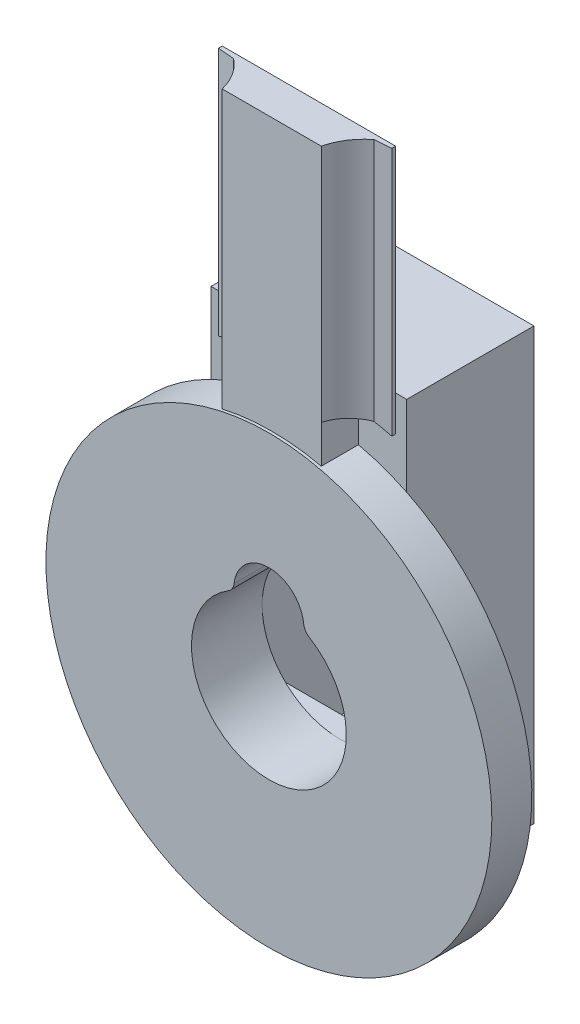
SolidWorks part; units mm, degrees
ref_plane "Front Plane" through (0, 0, 0) normal (0, 0, 1) x (1, 0, 0)
ref_plane "Top Plane" through (0, 0, 0) normal (0, 1, 0) x (1, 0, 0)
ref_plane "Right Plane" through (0, 0, 0) normal (1, 0, 0) x (0, 0, -1)
sketch "Croquis1" plane through (0, 0, 0) normal (0, 0, 1) x (1, 0, 0)
  circle A0 centre (0, 0) radius 18
extrude "Saliente-Extruir1" add sketch "Croquis1" along normal blind 3.5
sketch "Croquis2" plane through (0, 0, 0) normal (0, 0, 1) x (1, 0, 0)
  line L0 (-4, 17.5499) -> (-4, 39.1116)
  line L1 (4, 39.1116) -> (4, 17.5499)
  line L2 (-7, 19.799) -> (-7, 39.928)
  line L3 (-7, 39.928) -> (7, 39.928)
  line L4 (7, 39.928) -> (7, 19.799)
  line L5 (-4, 39.1116) -> (-4, 39.928)
  line L6 (4, 39.1116) -> (4, 39.928)
  arc A0 (4, 17.5499) -> (-4, 17.5499) centre (0, 0) ccw
  arc A1 (10.1584, 18.3795) -> (-10.1584, 18.3795) centre (0, 0) ccw
  arc A2 (-10.1584, 18.3795) -> (-7, 39.928) centre (-213.2982, 59.16) ccw
  arc A3 (10.1584, 18.3795) -> (7, 39.928) centre (213.2982, 59.16) cw
  dimension "D1" = 8
extrude "Saliente-Extruir5" add sketch "Croquis2" along normal blind 3.27 contours A1 L4 L3 L6 L1 | L1 A1 L0 A0 | A1 L1 L6 L3 L5 L0 | A1 L0 L5 L3 L2
ref_plane "Plano1" through (0, 40, 0) normal (0, 1, 0) x (1, 0, 0)
sketch "Croquis5" plane through (0, 40, 0) normal (0, 1, 0) x (1, 0, 0)
  line L1 (-7, -3.27) -> (-7, 0) construction
  line L9 (-7, 0) -> (-7, -0.27)
  line L10 (-7, -0.27) -> (7, -0.27)
  line L11 (7, -0.27) -> (7, 0)
  line L13 (7, 0) -> (-7, 0)
  line L15 (-7, -0.27) -> (-7, 0)
  line L16 (-7, -0.27) -> (-18.8879, -0.27)
  line L17 (-18.8879, -0.27) -> (-18.8879, 0.2021)
  line L18 (-18.8879, 0.2021) -> (18.2421, 0.2021)
  line L19 (18.2421, 0.2021) -> (18.2421, -0.27)
  line L20 (18.2421, -0.27) -> (7, -0.27)
extrude "Cortar-Extruir4" cut sketch "Croquis5" against normal up to surface (58.001 mm away) contours L11 L13 L9 L10 | L20 L19 L18 L17 L16 L9 L13 L11
sketch "Croquis4" plane through (0, 40, 0) normal (0, 1, 0) x (1, 0, 0)
  line L3 (-7, 0) -> (-7, -0.5733)
  line L5 (-4.4792, 0) -> (-7, 0)
  line L7 (0, 0) -> (0, -1.8016)
  line L8 (-4, -3.27) -> (-4.4792, 0)
  line L9 (-7, -0.5733) -> (-5.666, -0.685)
  line L10 (-7, 0) -> (-7, -3.27)
  line L11 (-7, -3.27) -> (-7, -0.27) construction
  line L12 (-4, -3.27) -> (-7, -3.27)
  line L13 (4, -3.27) -> (7, -3.27)
  line L14 (7, 0) -> (7, -3.27)
  line L15 (4.4792, 0) -> (7, 0)
  line L16 (4, -3.27) -> (4.4792, 0)
  line L17 (7, -0.5733) -> (5.666, -0.685)
  line L18 (7, 0) -> (7, -0.5733)
  line L19 (-7, -0.5733) -> (-7, -3.27)
  line L20 (0, -1.8016) -> (0, -3.27)
  line L21 (-4, -3.27) -> (4, -3.27) construction
  line L22 (0, -3.27) -> (-4, -3.27)
  line L23 (-7, -3.27) -> (7, -3.27) construction
  line L24 (0, -3.27) -> (4, -3.27)
  arc A2 (-5.666, -0.685) -> (-4, -3.27) centre (-8.5291, -4.3596) cw
  arc A3 (5.666, -0.685) -> (4, -3.27) centre (8.5291, -4.3596) ccw
  dimension "D1" = 4
  dimension "D2" = 4
extrude "Cortar-Extruir2" cut sketch "Croquis4" against normal blind 21 contours A2 L9 L10 L12 | L17 A3 L13 L14
sketch "Croquis6" plane through (0, 0, 0) normal (0, 0, 1) x (1, 0, 0)
  arc A0 (-3.2771, 5.3219) -> (3.2771, 5.3219) centre (0, 0) ccw
  arc A1 (2.8076, 6.0627) -> (-2.8076, 6.0627) centre (0, 5.75) ccw
  arc A2 (2.8076, 6.0627) -> (3.2771, 5.3219) centre (3.8015, 6.1734) ccw
  arc A3 (-2.8076, 6.0627) -> (-3.2771, 5.3219) centre (-3.8015, 6.1734) cw
extrude "Cortar-Extruir5" cut sketch "Croquis6" along normal blind 10
ref_plane "Plano2" through (0, 0, 0.27) normal (0, 0, -1) x (-1, 0, 0)
sketch "Croquis7" plane through (0, 0, 0) normal (0, 0, 1) x (1, 0, 0)
  arc A0 (-3.2771, 5.3219) -> (3.2771, 5.3219) centre (0, 0) ccw
  arc A1 (-2.8076, 6.0627) -> (2.8076, 6.0627) centre (0, 5.75) cw
  arc A2 (-3.2771, 5.3219) -> (-2.8076, 6.0627) centre (-3.8015, 6.1734) ccw
  arc A3 (2.8076, 6.0627) -> (3.2771, 5.3219) centre (3.8015, 6.1734) ccw
  arc A4 (-5.5967, 7.3647) -> (5.5967, 7.3647) centre (0, 0) ccw
  arc A5 (5.5967, 7.3647) -> (5.5967, 7.3647) centre (5.5967, 7.3647) ccw
  arc A6 (-5.5967, 7.3647) -> (5.5967, 7.3647) centre (0, 5.75) cw
  arc A7 (-5.5967, 7.3647) -> (-5.5967, 7.3647) centre (-5.5967, 7.3647) ccw
  dimension "D1" = 3
extrude "Saliente-Extruir6" add sketch "Croquis7" against normal blind 2.2
sketch "Croquis8" plane through (0, 0, 0.27) normal (0, 0, -1) x (-1, 0, 0)
  arc A0 (-5.5967, 7.3647) -> (5.5967, 7.3647) centre (0, 0) ccw
  arc A1 (-5.5967, 7.3647) -> (5.5967, 7.3647) centre (0, 5.75) cw
  circle A2 centre (0, 0) radius 18
extrude "Cortar-Extruir8" cut sketch "Croquis8" along normal blind 0.27 contours A2 A0 A1
sketch "Croquis9" plane through (0, 0, 0.27) normal (0, 0, -1) x (-1, 0, 0)
  line L0 (0, 0) -> (-6.3, 0)
  line L1 (-6.3, 5.2726) -> (-6.3, 19.8726)
  line L2 (-6.3, 19.8726) -> (6.3, 19.8726)
  line L3 (6.3, 19.8726) -> (6.3, -9.3274)
  line L4 (6.3, -9.3274) -> (0, -9.3274)
  line L5 (0, -9.3274) -> (-6.3, -9.3274)
  line L6 (-6.3, -9.3274) -> (-6.3, 5.2726)
  line L8 (-7.9, 5.2726) -> (-7.9, 21.4726)
  line L10 (7.9, 21.4726) -> (7.9, -10.9274)
  line L13 (-7.9, -10.9274) -> (-7.9, 5.2726)
  line L14 (-7.9, 21.4726) -> (-7.9, 22.6726)
  line L15 (-7.9, 22.6726) -> (7.9, 22.6726)
  line L16 (-7.9, -10.9274) -> (-7.9, -12.1274)
  line L17 (6.3, 16.5326) -> (-6.3, 16.5326)
  line L18 (6.3, -6.2774) -> (-6.3, -6.2774)
  line L19 (7.9, 21.4726) -> (7.9, 22.6726)
  line L20 (-7.9, -12.1274) -> (7.9, -12.1274)
  line L21 (-7.9, 21.4726) -> (7.9, 21.4726) construction
  line L22 (7.9, -12.1274) -> (7.9, -10.9274)
  line L24 (0, -10.9274) -> (-7.9, -10.9274) construction
  line L25 (7.9, -10.9274) -> (0, -10.9274) construction
  arc A0 (-3.2771, 5.3219) -> (3.2771, 5.3219) centre (0, 0) ccw
  arc A1 (3.2771, 5.3219) -> (2.8076, 6.0627) centre (3.8015, 6.1734) cw
  arc A3 (-3.2771, 5.3219) -> (-2.8076, 6.0627) centre (-3.8015, 6.1734) ccw
  arc A4 (2.8076, 6.0627) -> (-2.8076, 6.0627) centre (0, 5.75) ccw
  dimension "D1" = 14.6
  dimension "D2" = 14.6
  dimension "D3" = 6.3
  dimension "D4" = 6.3
  dimension "D5" = 1.6
  dimension "D6" = 1.2
  dimension "D7" = 1.2
extrude "Saliente-Extruir7" add sketch "Croquis9" along normal up to vertex (2.47 mm away)
sketch "Croquis10" plane through (0, 0, 0) normal (0, 0, 1) x (1, 0, 0)
  line L0 (0, 0) -> (-6.3, 0)
  line L1 (-6.3, 5.2726) -> (-6.3, 19.8726)
  line L2 (-6.3, 19.8726) -> (6.3, 19.8726)
  line L3 (6.3, 19.8726) -> (6.3, -9.3274)
  line L4 (6.3, -9.3274) -> (0, -9.3274)
  line L5 (0, -9.3274) -> (-6.3, -9.3274)
  line L6 (-6.3, -9.3274) -> (-6.3, 5.2726)
  line L7 (0, -10.9274) -> (0, -15.6274)
  line L8 (-7.9, 5.2726) -> (-7.9, 21.4726)
  line L9 (-6.3, 21.4726) -> (6.3, 21.4726)
  line L10 (7.9, 21.4726) -> (7.9, -10.9274)
  line L11 (6.3, -10.9274) -> (0, -10.9274)
  line L12 (0, -10.9274) -> (-6.3, -10.9274)
  line L13 (-7.9, -10.9274) -> (-7.9, 5.2726)
  line L14 (-7.9, 21.4726) -> (-7.9, 22.6726)
  line L15 (-7.9, 22.6726) -> (7.9, 22.6726)
  line L16 (7.9, 22.6726) -> (7.9, 21.4726)
  line L17 (6.3, 16.5326) -> (-6.3, 16.5326)
  line L18 (6.3, -6.2774) -> (-6.3, -6.2774)
  line L19 (-6.3, 19.8726) -> (-6.3, 21.4726)
  line L20 (6.3, 19.8726) -> (6.3, 21.4726)
  line L21 (-7.9, -10.9274) -> (-7.9, -12.1274)
  line L22 (-7.9, -12.1274) -> (7.9, -12.1274)
  line L23 (7.9, -12.1274) -> (7.9, -10.9274)
  line L24 (-6.3, -9.3274) -> (-6.3, -10.9274)
  line L25 (6.3, -9.3274) -> (6.3, -10.9274)
  line L27 (7.9, -10.9274) -> (0, -10.9274) construction
  line L28 (0, -10.9274) -> (-7.9, -10.9274) construction
  line L29 (-7.9, 21.4726) -> (7.9, 21.4726) construction
  arc A0 (-3.2771, 5.3219) -> (3.2771, 5.3219) centre (0, 0) ccw
  arc A1 (3.2771, 5.3219) -> (2.8076, 6.0627) centre (3.8015, 6.1734) cw
  arc A3 (-3.2771, 5.3219) -> (-2.8076, 6.0627) centre (-3.8015, 6.1734) ccw
  arc A4 (2.8076, 6.0627) -> (-2.8076, 6.0627) centre (0, 5.75) ccw
  dimension "D1" = 14.6
  dimension "D2" = 14.6
  dimension "D3" = 6.3
  dimension "D4" = 6.3
  dimension "D5" = 1.6
  dimension "D6" = 1.2
  dimension "D7" = 1.2
extrude "Saliente-Extruir9" add sketch "Croquis10" against normal blind 10 contours L13 L12 L11 L10 L9 L8 L5 L6 L1 L2 L3 L4
sketch "Croquis11" plane through (0, 0, 0.27) normal (0, 0, -1) x (-1, 0, 0)
  line L10 (7.9, 4.8117) -> (7.9, -4.8117)
  line L13 (-7.9, -4.8117) -> (-7.9, 4.8117)
  arc A2 (-7.9, -4.8117) -> (-7.9, 4.8117) centre (0, 0) cw
  arc A5 (7.9, -4.8117) -> (7.9, 4.8117) centre (0, 0) ccw
  point P5 (-7.9, 5.2726)
  point P6 (-7.9, 21.4726)
  point P7 (7.9, 21.4726)
  point P8 (7.9, -10.9274)
  point P9 (0, -10.9274)
  point P10 (-7.9, -10.9274)
  point P17 (-6.3, 5.2726)
  point P18 (6.3, -9.3274)
  point P19 (-6.3, 19.8726)
  point P20 (6.3, 19.8726)
  point P21 (-6.3, -9.3274)
extrude "Cortar-Extruir9" cut sketch "Croquis11" along normal blind 10
sketch "Croquis13" plane through (0, 0, 0) normal (0, 0, 1) x (1, 0, 0)
  line L0 (-6.25, 0) -> (-6.3, 0)
  line L1 (-6.3, 16.6326) -> (-6.3, 19.8726)
  line L3 (6.3, 19.8726) -> (6.3, 16.6326)
  line L6 (-6.3, -9.3274) -> (-6.3, -6.2774)
  line L7 (6.3, -6.2774) -> (6.3, -9.3274)
  line L9 (-6.3, 21.4726) -> (6.3, 21.4726)
  line L11 (6.3, -10.9274) -> (0, -10.9274)
  line L12 (0, -10.9274) -> (-6.3, -10.9274)
  line L18 (6.3, -6.2774) -> (-6.3, -6.2774)
  line L19 (-6.3, 19.8726) -> (-6.3, 21.4726)
  line L20 (6.3, 19.8726) -> (6.3, 21.4726)
  line L24 (-6.3, -9.3274) -> (-6.3, -10.9274)
  line L25 (6.3, -9.3274) -> (6.3, -10.9274)
  line L27 (7.9, -10.9274) -> (0, -10.9274) construction
  line L28 (0, -10.9274) -> (-7.9, -10.9274) construction
  line L29 (-7.9, 21.4726) -> (7.9, 21.4726) construction
  line L30 (0, -9.3274) -> (-6.3, -9.3274) construction
  line L31 (6.3, -9.3274) -> (0, -9.3274) construction
  line L32 (-6.3, 19.8726) -> (6.3, 19.8726) construction
  line L33 (-7.9, -10.9274) -> (-7.9, 5.2726) construction
  line L34 (-7.9, 5.2726) -> (-7.9, 21.4726) construction
  line L35 (6.3, 19.8726) -> (6.3, -9.3274) construction
  line L36 (-6.3, -9.3274) -> (-6.3, 5.2726) construction
  line L37 (-6.3, 5.2726) -> (-6.3, 19.8726) construction
  line L38 (7.9, 21.4726) -> (7.9, -10.9274) construction
  line L39 (-6.3, 16.6326) -> (6.3, 16.6326)
  dimension "D5" = 1.6
extrude "Saliente-Extruir10" add sketch "Croquis13" against normal blind 4
sketch "Croquis12" plane through (0, 0, 0.27) normal (0, 0, -1) x (-1, 0, 0)
  line L2 (7.9, 22.6726) -> (7.9, -12.1274)
  line L3 (7.9, -12.1274) -> (7.9, 5.2726)
  line L4 (7.9, 5.2726) -> (0, 5.2726)
  circle A0 centre (0, 18.8326) radius 1
  circle A1 centre (0, -8.2874) radius 1
extrude "Cortar-Extruir10" cut sketch "Croquis12" along normal blind 18.85 contours A0 | A1
